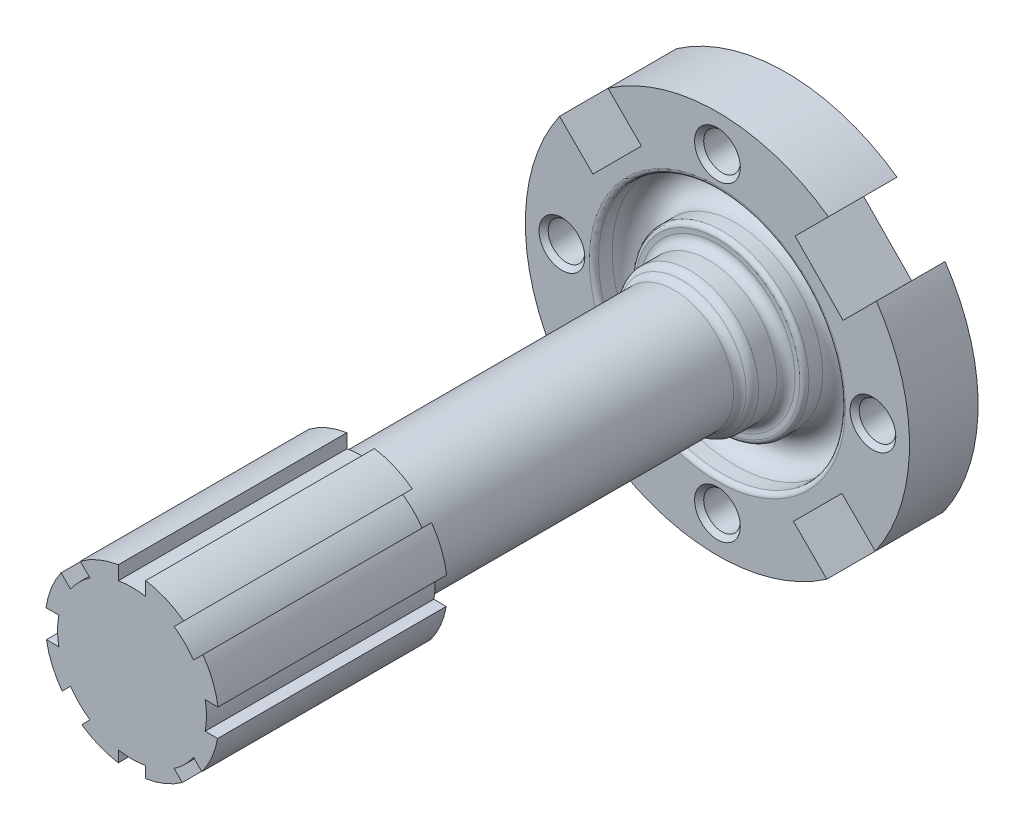
SolidWorks part; units mm, degrees
material "Plain Carbon Steel"
ref_plane "Front Plane" through (0, 0, 0) normal (0, 0, 1) x (1, 0, 0)
ref_plane "Top Plane" through (0, 0, 0) normal (0, 1, 0) x (1, 0, 0)
ref_plane "Right Plane" through (0, 0, 0) normal (1, 0, 0) x (0, 0, -1)
sketch "Sketch1" plane through (0, 0, 0) normal (1, 0, 0) x (0, 0, -1)
  line L0 (0, 0) -> (-23, 0) construction
  line L1 (-23, 0) -> (-23, 15)
  line L2 (-23, 15) -> (-15, 15)
  line L3 (-15, 15) -> (-15, 19)
  line L4 (-15, 42) -> (0, 42)
  line L5 (0, 42) -> (0, 25.002)
  line L6 (0, 0) -> (0, 25.002) construction
  line L7 (0, 25.002) -> (-3.3, 25.002)
  line L8 (-3.3, 25.002) -> (-5.4874, 0)
  line L9 (-23, 0) -> (-5.4874, 0)
  line L10 (-11, 27) -> (-15, 27)
  line L11 (-11, 19) -> (-15, 19)
  line L12 (-15, 27) -> (-15, 42)
  arc A0 (-11, 19) -> (-11, 27) centre (-11, 23) ccw
  point P5 (-11.5, 0)
  point P12 (-1.65, 25.002)
  dimension "D8" = 23
  dimension "D4" = 4
  dimension "D9" = 4
  dimension "D1" = 15
  dimension "D2" = 42
  dimension "D3" = 15
  dimension "D5" = 1.65
  dimension "D6" = 25.002
  dimension "D7" = 5
  dimension "D10" = 4
  dimension "D11" = 4
revolve "Revolve1" add sketch "Sketch1" angle 360 about L9
sketch "Sketch4" plane through (0, 0, 23) normal (0, 0, 1) x (1, 0, 0)
  circle A0 centre (0, 0) radius 34
  circle A1 centre (0, 0) radius 15 construction
  point P5 (0, 34)
  point P7 (-34, 0)
  point P9 (0, -34)
  point P11 (34, 0)
  dimension "D1" = 68
hole_wizard "Ø8.0mm Dowel Hole1" positions "Sketch4" profile "Sketch5" hole size "Ø8.0" standard "ANSI Metric" end condition through all
sketch "Sketch5" plane through (34, 0, 23) normal (1, 0, 0) x (0, -1, 0)
  line L0 (0, 0) -> (0, 23)
  line L1 (0, 23) -> (4, 23)
  line L2 (4, 23) -> (4, 0.025)
  line L3 (4, 0.025) -> (4.025, 0)
  line L5 (4.025, 0) -> (0, 0)
  line L6 (-4, 0.025) -> (-4.025, 0) construction
  line L11 (0, -6.35) -> (0, 107.95) construction
  dimension "Thru Hole Dia." = 8
  dimension "Thru Hole Depth" = 23
  dimension "Near C'Sink Dia." = 8.05
  dimension "Near C'Sink Angle" = 90
sketch "Sketch6" plane through (0, 0, 23) normal (0, 0, 1) x (1, 0, 0)
  line L0 (0, 44.058) -> (0, -44.058) construction
  line L1 (-49.9171, 0) -> (49.9171, 0) construction
  line L2 (33.8908, 33.8908) -> (-33.8908, -33.8908) construction
  line L3 (-34.0631, 34.0631) -> (34.0631, -34.0631) construction
  point P7 (0, 0)
  point P11 (0, 0)
  point P14 (0, 0)
  point P17 (0, 0)
sketch "Sketch8" plane through (0, 0, 15) normal (0, 0, 1) x (1, 0, 0)
  line L0 (33.8908, 33.8908) -> (-33.8908, -33.8908) construction
  line L1 (-34.0631, 34.0631) -> (34.0631, -34.0631) construction
  line L3 (-16.6171, 27.2236) -> (-23.9179, 34.5244)
  line L4 (-16.6171, 27.2236) -> (-27.2245, 16.6161)
  line L5 (-27.2245, 16.6161) -> (-34.5252, 23.9168)
  circle A0 centre (0, 0) radius 42 construction
  point P0 (-16.6171, 27.2236)
  dimension "D1" = 31
  dimension "D2" = 7.4999
  dimension "D3" = 10.3249
extrude "Cut-Extrude1" cut sketch "Sketch8" against normal through all and the other way through all flip side to cut
ref_plane "Plane1" through (0, 0, 0) normal (-0.7071, 0.7071, 0) x (-0.7071, -0.7071, 0)
mirror "Mirror1" about plane through (0, 0, 0) normal (-0.7071, 0.7071, 0) of "Cut-Extrude1"
sketch "Sketch9" plane through (0, 0, 15) normal (0, 0, 1) x (1, 0, 0)
  line L0 (16.9748, 26.979) -> (27.4705, 16.265)
  line L2 (27.4705, 16.265) -> (34.7684, 23.5618)
  line L3 (16.9748, 26.979) -> (24.2721, 34.2763)
  arc A0 (34.5244, -23.9179) -> (-23.9179, 34.5244) centre (0, 0) ccw construction
  dimension "D1" = 14.9983
  dimension "D2" = 10.32
  dimension "D3" = 10.32
extrude "Cut-Extrude2" cut sketch "Sketch9" against normal through all and the other way through all flip side to cut
ref_plane "Plane4" through (0, 0, 0) normal (-0.7071, -0.7071, 0) x (0.7071, -0.7071, 0)
mirror "Mirror4" about plane through (0, 0, 0) normal (-0.7071, -0.7071, 0) of "Cut-Extrude2"
sketch "Sketch12" plane through (0, 0, 23) normal (0, 0, 1) x (1, 0, 0)
  circle A0 centre (0, 0) radius 13
  circle A1 centre (0, 0) radius 15 construction
  dimension "D1" = 26
extrude "Boss-Extrude3" add sketch "Sketch12" along normal blind 70
sketch "Sketch16" plane through (0, 0, 93) normal (0, 0, 1) x (1, 0, 0)
  circle A0 centre (0, 0) radius 19
extrude "Boss-Extrude4" add sketch "Sketch16" along normal blind 50
sketch "Sketch18" plane through (0, 0, 143) normal (0, 0, 1) x (1, 0, 0)
  line L0 (0, 19) -> (0, -19) construction
  line L6 (-3, 21.7162) -> (3, 21.7162)
  line L7 (-3, 21.7162) -> (-3, 15.7162)
  line L9 (3, 21.7162) -> (3, 15.7162)
  line L10 (0, 15.7162) -> (0, 21.7162) construction
  line L11 (-3, 18.7162) -> (3, 18.7162) construction
  circle A0 centre (0, 0) radius 19 construction
  circle A1 centre (0, 0) radius 16
  point P10 (0, 0)
  point P13 (0, 18.7162)
  circle M5 centre (0, 0) radius 19
  dimension "D1" = 6
  dimension "D3" = 32
  dimension "D2" = 6
extrude "Cut-Extrude5" cut sketch "Sketch18" against normal blind 50 contours A1 L9 L7 M5
pattern_circular "CirPattern2" count 8 over 360 about axis through (0, -0.2823, 0) along (0, 0, 1) of "Cut-Extrude5"
fillet "Fillet1" radius 2 3 edges at (0, -15, 23) (0, -15, 15) (13, 0, 93)
fillet "Fillet2" radius 2 1 edges at (13, 0, 23)
fillet "Fillet3" radius 1 1 edges at (0, -19, 15)
fillet "Fillet4" radius 1 1 edges at (0, -27, 15)
chamfer "Chamfer2" distance 1 angle 45 4 edges at (34, 4, 15) (0, 38, 15) (-34, 4, 15) (0, -30, 15)
